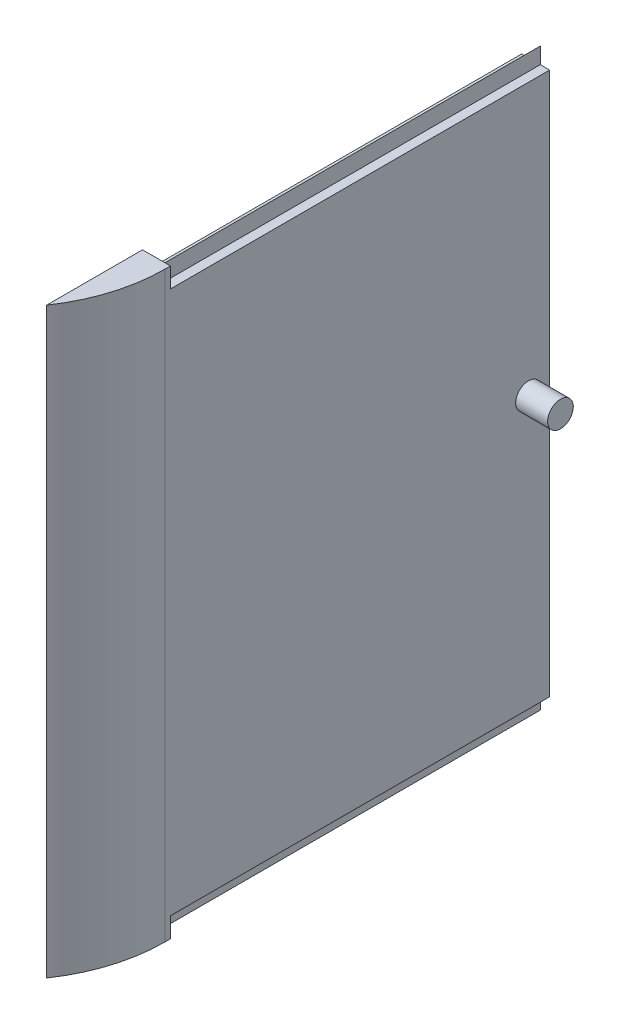
SolidWorks part; units mm, degrees
ref_plane "Front Plane" through (0, 0, 0) normal (0, 0, 1) x (1, 0, 0)
ref_plane "Top Plane" through (0, 0, 0) normal (0, 1, 0) x (1, 0, 0)
ref_plane "Right Plane" through (0, 0, 0) normal (1, 0, 0) x (0, 0, -1)
sketch "Sketch1" plane through (0, 0, 0) normal (0, 0, 1) x (1, 0, 0)
  line L0 (37.6679, -148) -> (40, -148) construction
  line L1 (37.6679, -152.0471) -> (37.6679, -148) construction
  line L2 (33, -148) -> (33.6841, -148) construction
  line L3 (33.6841, -148) -> (37.6679, -152.0471) construction
  line L4 (37.6679, -12) -> (40, -12) construction
  line L5 (33, -12) -> (33.6841, -12) construction
  line L6 (33.6841, -12) -> (37.6679, -7.9529) construction
  line L7 (37.6679, -7.9529) -> (37.6679, -12) construction
  line L8 (37.6679, -148) -> (40, -148)
  line L9 (37.6679, -152.0471) -> (37.6679, -148)
  line L10 (33, -148) -> (33.6841, -148)
  line L11 (33.6841, -148) -> (37.6679, -152.0471)
  line L12 (37.6679, -12) -> (40, -12)
  line L13 (33, -12) -> (33.6841, -12)
  line L14 (33.6841, -12) -> (37.6679, -7.9529)
  line L15 (37.6679, -7.9529) -> (37.6679, -12)
  line L16 (40, -12) -> (40, -148)
  line L17 (33, -148) -> (33, -12)
extrude "Boss-Extrude1" add sketch "Sketch1" against normal up to surface (95.0113 mm away)
sketch "Sketch4" plane through (0, 0, 0) normal (0, 0, 1) x (1, 0, 0)
  line L0 (33, -12) -> (33, -4) construction
  line L1 (40, -153) -> (33, -153)
  line L2 (40, -153) -> (40, -7)
  line L3 (40, -7) -> (33, -7)
  line L4 (33, -153) -> (33, -7)
extrude "Boss-Extrude2" add sketch "Sketch4" along normal blind 24
fillet "Fillet1" radius 40 1 edges at (40, -80, 24)
sketch "Sketch5" plane through (40, 0, 0) normal (1, 0, 0) x (0, 0, -1)
  line L0 (89.7148, -12) -> (89.7148, -148) construction
  line L1 (95.0113, -12) -> (0, -12) construction
  line L2 (95.0113, -148) -> (0, -148) construction
  circle A0 centre (89.7148, -80) radius 3.2191
extrude "Boss-Extrude3" add sketch "Sketch5" along normal blind 8
